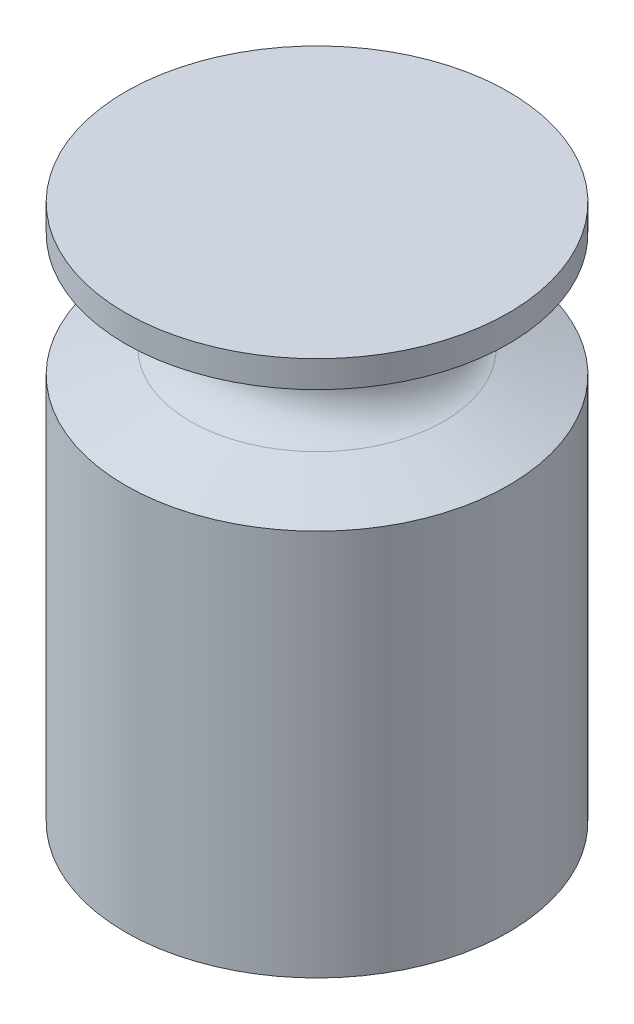
SolidWorks part; units mm, degrees
ref_plane "Front Plane" through (0, 0, 0) normal (0, 0, 1) x (1, 0, 0)
ref_plane "Top Plane" through (0, 0, 0) normal (0, 1, 0) x (1, 0, 0)
ref_plane "Right Plane" through (0, 0, 0) normal (1, 0, 0) x (0, 0, -1)
sketch "Sketch1" plane through (0, 0, 0) normal (0, 1, 0) x (1, 0, 0)
  circle A0 centre (0, 0) radius 25
  dimension "D1" = 50
extrude "Boss-Extrude1" add sketch "Sketch1" along normal blind 70
sketch "Sketch2" plane through (0, 0, 0) normal (1, 0, 0) x (0, 0, -1)
  line L0 (25, 50.5) -> (16.533, 53.5)
  line L1 (25, 66.5) -> (16.533, 63.5)
  line L2 (25, 0) -> (25, 70) construction
  line L3 (25, 58.5) -> (13, 58.5) construction
  line L4 (25, 70) -> (-25, 70) construction
  line L5 (25, 66.5) -> (25, 50.5)
  arc A0 (16.533, 63.5) -> (13, 58.5) centre (18.3046, 58.5) ccw
  arc A1 (16.533, 53.5) -> (13, 58.5) centre (18.3046, 58.5) cw
  point P10 (14.5116, 62.1674)
  point P11 (0, 0)
  point P14 (15.5916, 62.4407)
  dimension "D1" = 3.5
  dimension "D2" = 12
  dimension "D3" = 8
  dimension "D4" = 10
ref_axis "Axis1" through (0, 73.5, 0) along (0, -1, 0)
revolve "Cut-Revolve1" cut sketch "Sketch2" angle 360 about axis through (0, 73.5, 0) along (0, -1, 0)
